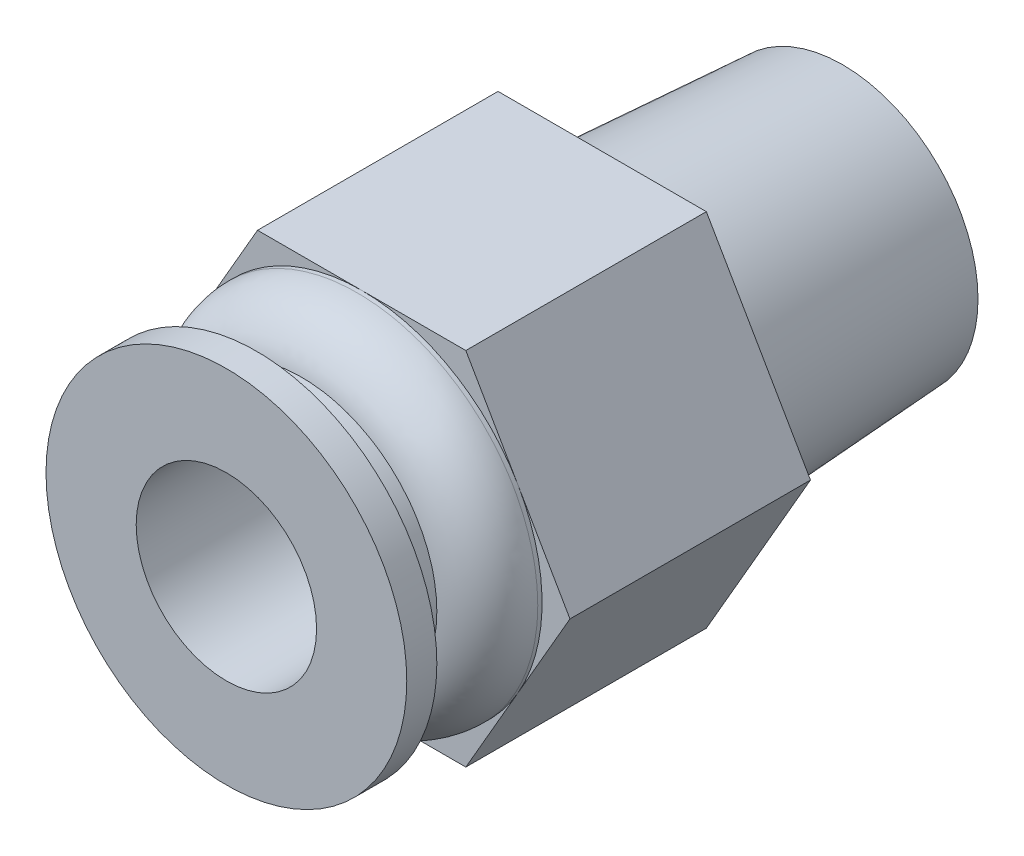
SolidWorks part; units mm, degrees
ref_plane "Front Plane" through (0, 0, 0) normal (0, 0, 1) x (1, 0, 0)
ref_plane "Top Plane" through (0, 0, 0) normal (0, 1, 0) x (1, 0, 0)
ref_plane "Right Plane" through (0, 0, 0) normal (1, 0, 0) x (0, 0, -1)
sketch "Sketch1" plane through (0, 0, 0) normal (0, 0, 1) x (1, 0, 0)
  circle A0 centre (0, 0) radius 4.5
  dimension "D1" = 9
extrude "Boss-Extrude1" add sketch "Sketch1" along normal blind 8 draft 3.5 draft outward yes
sketch "Sketch2" plane through (0, 0, 8) normal (0, 0, 1) x (1, 0, 0)
  line L1 (6.9282, 0) -> (3.4641, 6)
  line L2 (3.4641, 6) -> (-3.4641, 6)
  line L3 (-3.4641, 6) -> (-6.9282, 0)
  line L4 (-6.9282, 0) -> (-3.4641, -6)
  line L5 (-3.4641, -6) -> (3.4641, -6)
  line L6 (3.4641, -6) -> (6.9282, 0)
  circle A0 centre (0, 0) radius 6 construction
  dimension "D1" = 12
extrude "Boss-Extrude2" add sketch "Sketch2" along normal blind 8
sketch "Sketch3" plane through (0, 0, 16) normal (0, 0, 1) x (1, 0, 0)
  circle A0 centre (0, 0) radius 6
  dimension "D1" = 12
extrude "Boss-Extrude3" add sketch "Sketch3" along normal blind 2
sketch "Sketch9" plane through (0, 0, 18) normal (0, 0, 1) x (1, 0, 0)
  circle A0 centre (0, 0) radius 4.5
  dimension "D1" = 9
extrude "Boss-Extrude6" add sketch "Sketch9" along normal blind 0.5
fillet "Fillet1" radius 1.9 1 edges at (6, 0, 18) first distance on face at (6, 0, 18)
sketch "Sketch4" plane through (0, 0, 18.5) normal (0, 0, 1) x (1, 0, 0)
  circle A0 centre (0, 0) radius 3.75
  dimension "D1" = 7.5
extrude "Boss-Extrude4" add sketch "Sketch4" along normal blind 1
sketch "Sketch5" plane through (0, 0, 19.5) normal (0, 0, 1) x (1, 0, 0)
  circle A0 centre (0, 0) radius 6
  dimension "D1" = 12
extrude "Boss-Extrude5" add sketch "Sketch5" along normal blind 1
sketch "Sketch6" plane through (0, 0, 20.5) normal (0, 0, 1) x (1, 0, 0)
  circle A0 centre (0, 0) radius 3
  dimension "D1" = 6
extrude "Cut-Extrude1" cut sketch "Sketch6" against normal offset from surface (8.5 mm away) 4 up to face at (6.0415, 0, 16) offset beyond the face yes
sketch "Sketch7" plane through (0, 0, 12) normal (0, 0, 1) x (1, 0, 0)
  line L1 (0, -2.3094) -> (2, -1.1547)
  line L2 (2, -1.1547) -> (2, 1.1547)
  line L3 (2, 1.1547) -> (0, 2.3094)
  line L4 (0, 2.3094) -> (-2, 1.1547)
  line L5 (-2, 1.1547) -> (-2, -1.1547)
  line L6 (-2, -1.1547) -> (0, -2.3094)
  circle A0 centre (0, 0) radius 2 construction
  dimension "D1" = 4
extrude "Cut-Extrude2" cut sketch "Sketch7" against normal offset from surface (8 mm away) 4 up to face at (4.9893, 0, 8) offset beyond the face yes
sketch "Sketch8" plane through (0, 0, 0) normal (0, 0, -1) x (-1, 0, 0)
  circle A0 centre (0, 0) radius 3.175
  dimension "D1" = 6.35
extrude "Cut-Extrude3" cut sketch "Sketch8" against normal up to surface (4 mm away) up to face at (0, 0, 4)
